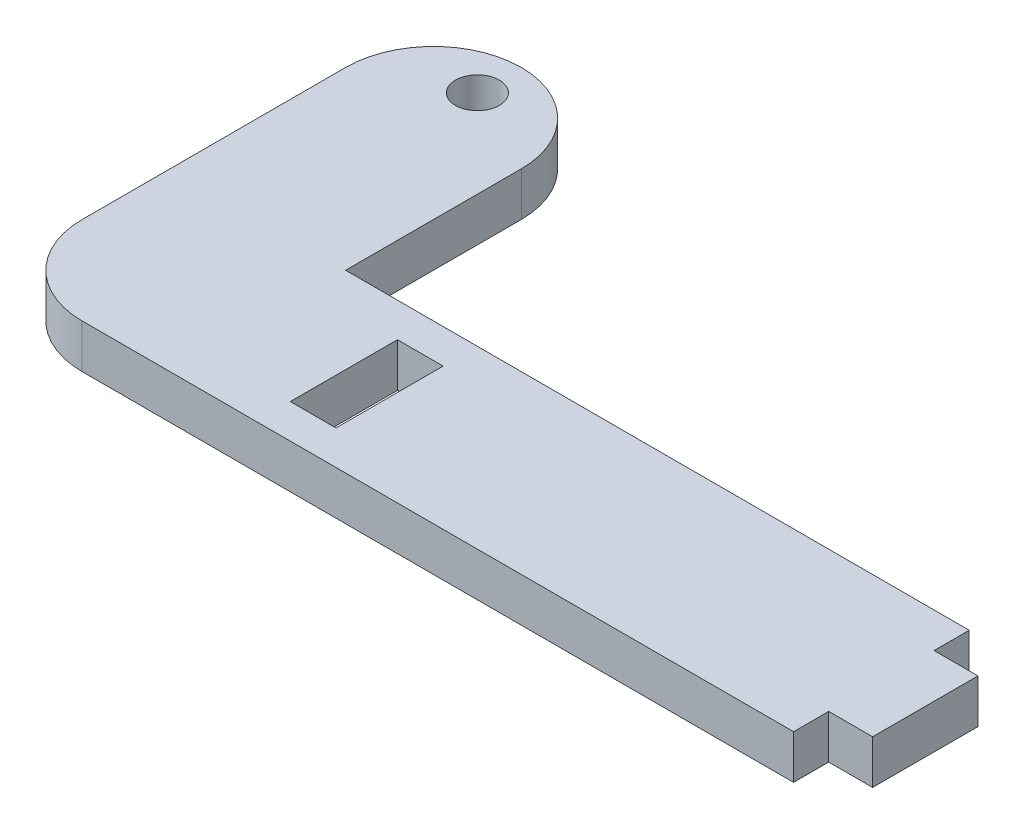
SolidWorks part; units mm, degrees
ref_plane "Front Plane" through (0, 0, 0) normal (0, 0, 1) x (1, 0, 0)
ref_plane "Top Plane" through (0, 0, 0) normal (0, 1, 0) x (1, 0, 0)
ref_plane "Right Plane" through (0, 0, 0) normal (1, 0, 0) x (0, 0, -1)
sketch "Sketch1" plane through (0, 0, 0) normal (0, 1, 0) x (1, 0, 0)
  line L0 (30.48, 6.35) -> (-17.78, 6.35)
  line L1 (-30.48, 6.35) -> (30.48, 6.35) construction
  line L2 (-30.48, 6.35) -> (-30.48, -6.35)
  line L3 (-30.48, -6.35) -> (30.48, -6.35)
  line L4 (30.48, 6.35) -> (30.48, -6.35)
  line L5 (-11.557, 3.8735) -> (-8.255, 3.8735)
  line L6 (-11.557, 3.8735) -> (-11.557, -3.8735)
  line L7 (-11.557, -3.8735) -> (-8.255, -3.8735)
  line L8 (-8.255, 3.8735) -> (-8.255, -3.8735)
  line L9 (-30.48, 6.35) -> (-17.78, 6.35) construction
  line L10 (-30.48, 6.35) -> (-30.48, 25.4)
  line L11 (-30.48, 25.4) -> (-17.78, 25.4)
  line L12 (-17.78, 6.35) -> (-17.78, 25.4)
  circle A0 centre (-24.13, 22.225) radius 1.5875
  point P4 (0, 6.35)
  point P5 (30.48, 0)
  dimension "D3" = 3.175
  dimension "D1" = 60.96
  dimension "D2" = 12.7
  dimension "D4" = 6.35
  dimension "D5" = 19.05
  dimension "D6" = 3.302
  dimension "D7" = 7.747
  dimension "D8" = 2.4765
  dimension "D9" = 38.735
  dimension "D10" = 12.7
  dimension "D11" = 3.175
extrude "Boss-Extrude1" add sketch "Sketch1" along normal blind 3.175
sketch "Sketch3" plane through (0, 3.175, 0) normal (0, 1, 0) x (1, 0, 0)
  line L2 (30.48, 6.35) -> (27.305, 6.35)
  line L3 (30.48, 6.35) -> (30.48, 3.81)
  line L4 (30.48, 3.81) -> (27.305, 3.81)
  line L7 (27.305, 6.35) -> (27.305, 3.81)
  line L8 (30.48, -6.35) -> (27.305, -6.35)
  line L9 (30.48, -6.35) -> (30.48, -3.81)
  line L10 (30.48, -3.81) -> (27.305, -3.81)
  line L11 (27.305, -6.35) -> (27.305, -3.81)
  dimension "D1" = 2.54
  dimension "D2" = 3.175
  dimension "D3" = 2.54
  dimension "D4" = 3.175
extrude "Cut-Extrude1" cut sketch "Sketch3" against normal blind 3.175
fillet "Fillet1" radius 6.35 1 edges at (-30.48, 1.5875, -25.4) type face fillet first side face at (-24.13, 1.5875, -25.4) second side face at (-30.48, 1.5875, -9.525)
fillet "Fillet2" radius 6.35 1 edges at (-17.78, 1.5875, -25.4) type face fillet first side face at (-20.955, 1.5875, -25.4) second side face at (-17.78, 1.5875, -15.875)
fillet "Fillet3" radius 6.35 1 edges at (-30.48, 1.5875, 6.35) type face fillet first side face at (-30.48, 1.5875, -6.35) second side face at (-1.5875, 1.5875, 6.35)
equation "\"D3@Sketch3\"=\"D1@Sketch3\""
equation "\"D4@Sketch3\"=\"D2@Sketch3\""
